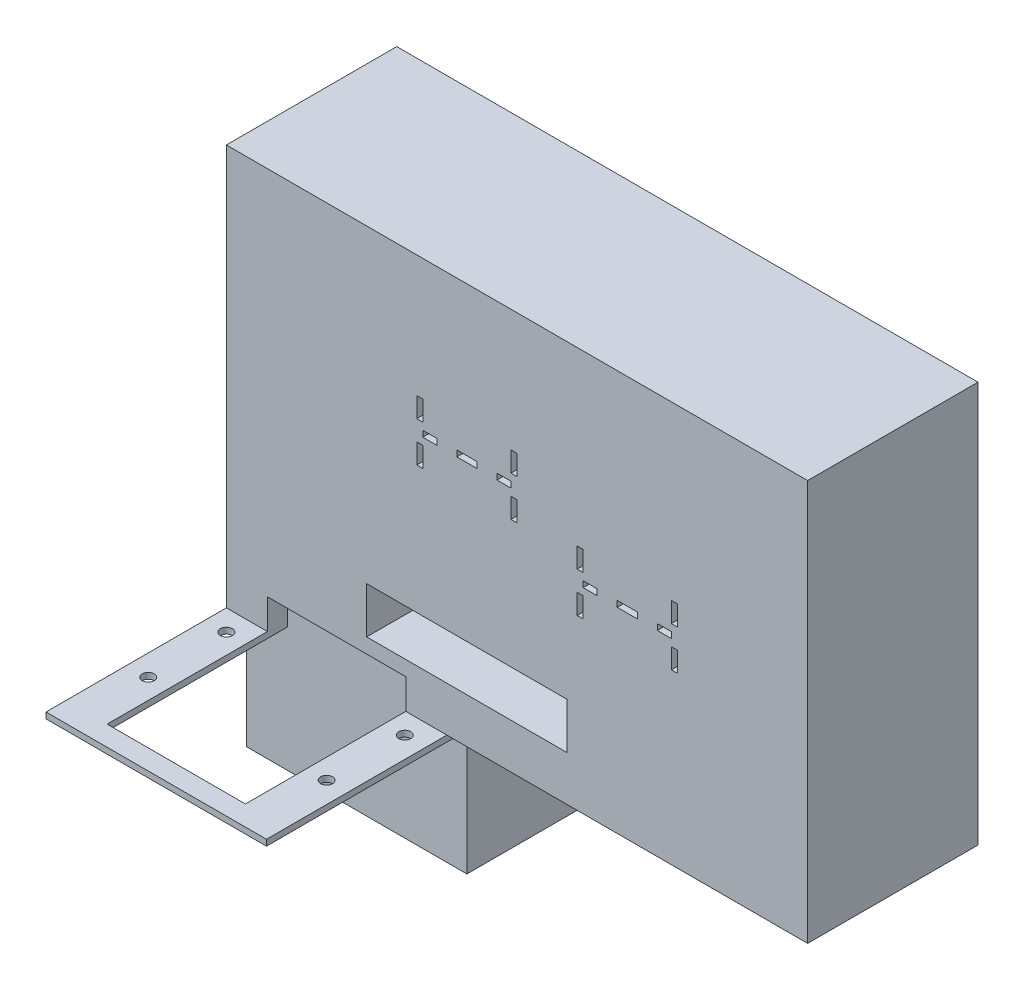
SolidWorks part; units mm, degrees
material "Cedro"
ref_plane "Alzado" through (0, 0, 0) normal (0, 0, 1) x (1, 0, 0)
ref_plane "Planta" through (0, 0, 0) normal (0, 1, 0) x (1, 0, 0)
ref_plane "Vista lateral" through (0, 0, 0) normal (1, 0, 0) x (0, 0, -1)
sketch "Croquis1" plane through (0, 0, 0) normal (0, 0, 1) x (1, 0, 0)
  line L1 (-85.6349, 58.6584) -> (24.3651, 58.6584)
  line L2 (-85.6349, 58.6584) -> (-85.6349, -6.3416)
  line L3 (-85.6349, -6.3416) -> (24.3651, -6.3416)
  line L4 (24.3651, 58.6584) -> (24.3651, -6.3416)
  line L5 (-85.6349, 58.6584) -> (24.3651, -6.3416) construction
  line L6 (-85.6349, -6.3416) -> (24.3651, 58.6584) construction
  point P0 (-30.6349, 26.1584)
  dimension "D1" = 65
  dimension "D2" = 110
extrude "Saliente-Extruir1" add sketch "Croquis1" along normal blind 75
sketch "Croquis3" plane through (0, 0, 75) normal (0, 0, 1) x (1, 0, 0)
  line L0 (-85.6349, 58.6584) -> (24.3651, 58.6584)
  line L1 (-85.6349, 58.6584) -> (-85.6349, 55.6584)
  line L2 (-85.6349, 58.6584) -> (-85.6349, -6.3416) construction
  line L3 (-85.6349, 55.6584) -> (24.3651, 55.6584)
  line L4 (24.3651, -6.3416) -> (24.3651, 58.6584) construction
  line L5 (24.3651, 55.6584) -> (24.3651, 58.6584)
  dimension "D1" = 3
extrude "Saliente-Extruir2" add sketch "Croquis3" along normal blind 70
sketch "Croquis4" plane through (0, 55.6584, 0) normal (0, -1, 0) x (1, 0, 0)
  line L3 (-65.1349, 134.5) -> (-65.1349, 75)
  line L6 (-85.6349, 75) -> (24.3651, 75) construction
  line L7 (-65.1349, 134.5) -> (-65.1349, 145)
  line L8 (-85.6349, 145) -> (24.3651, 145) construction
  line L9 (-65.1349, 75) -> (3.8651, 75)
  line L11 (-65.1349, 145) -> (3.8651, 145)
  line L13 (3.8651, 138) -> (3.8651, 145)
  line L14 (3.8651, 138) -> (3.8651, 75)
  circle A0 centre (-75.1349, 134.5) radius 3
  circle A1 centre (-75.1349, 95.5) radius 3
  circle A2 centre (13.8651, 134.5) radius 3
  circle A3 centre (13.8651, 95.5) radius 3
  dimension "D5" = 6
  dimension "D6" = 6
  dimension "D7" = 6
  dimension "D8" = 6
  dimension "D1" = 10
  dimension "D3" = 39
  dimension "D4" = 89
extrude "Cortar-Extruir1" cut sketch "Croquis4" against normal blind 70
sketch "Croquis6" plane through (0, 58.6584, 0) normal (0, 1, 0) x (1, 0, 0)
  line L0 (-85.6349, -145) -> (-85.6349, -175)
  line L1 (-85.6349, -175) -> (24.3651, -175)
  line L2 (24.3651, -175) -> (24.3651, -145)
  line L3 (24.3651, -145) -> (3.8651, -145)
  line L4 (-65.1349, -145) -> (-65.1349, -165)
  line L5 (-65.1349, -165) -> (3.8651, -165)
  line L6 (3.8651, -165) -> (3.8651, -145)
  line L7 (-65.1349, -145) -> (-85.6349, -145)
  dimension "D1" = 30
  dimension "D2" = 20
extrude "Saliente-Extruir3" add sketch "Croquis6" against normal blind 3
sketch "Croquis7" plane through (0, 58.6584, 0) normal (0, 1, 0) x (1, 0, 0)
  line L0 (-85.6349, 0) -> (204.3651, 0)
  line L1 (-85.6349, 0) -> (-85.6349, -85)
  line L2 (-85.6349, -175) -> (-85.6349, 0) construction
  line L3 (-85.6349, -85) -> (204.3651, -85)
  line L4 (204.3651, -85) -> (204.3651, 0)
  dimension "D1" = 290
  dimension "D2" = 85
extrude "Saliente-Extruir4" add sketch "Croquis7" along normal blind 200
sketch "Croquis8" plane through (0, 0, 85) normal (0, 0, 1) x (1, 0, 0)
  line L0 (-65.1349, 58.6584) -> (-65.1349, 73.6584)
  line L1 (-65.1349, 73.6584) -> (3.8651, 73.6584)
  line L2 (3.8651, 58.6584) -> (3.8651, 73.6584)
  line L3 (-65.1349, 58.6584) -> (3.8651, 58.6584)
  dimension "D1" = 15
  dimension "D2" = 15
extrude "Cortar-Extruir2" cut sketch "Croquis8" against normal blind 10
sketch "Croquis10" plane through (0, 0, 85) normal (0, 0, 1) x (1, 0, 0)
  line L1 (-0.6349, 81.0942) -> (-15.6349, 81.0942)
  line L2 (69.3651, 81.0942) -> (-0.6349, 81.0942)
  line L4 (-15.6349, 81.0942) -> (-15.6349, 104.0942)
  line L5 (-15.6349, 104.0942) -> (-0.6349, 104.0942)
  line L6 (69.3651, 81.0942) -> (84.3651, 81.0942)
  line L7 (69.3651, 104.0942) -> (-0.6349, 104.0942)
  line L8 (84.3651, 81.0942) -> (84.3651, 104.0942)
  line L11 (84.3651, 104.0942) -> (69.3651, 104.0942)
  dimension "D1" = 15
  dimension "D3" = 15
extrude "Cortar-Extruir3" cut sketch "Croquis10" against normal blind 50
sketch "Croquis12" plane through (0, 0, 85) normal (0, 0, 1) x (1, 0, 0)
  line L0 (34.3651, 104.0942) -> (34.3651, 258.6584) construction
  line L1 (84.3651, 104.0942) -> (-15.6349, 104.0942) construction
  line L2 (-85.6349, 258.6584) -> (204.3651, 258.6584) construction
  line L3 (29.3651, 181.3763) -> (39.3651, 181.3763)
  line L4 (39.3651, 181.3763) -> (39.3651, 184.3763)
  line L5 (39.3651, 184.3763) -> (29.3651, 184.3763)
  line L6 (39.3651, 181.3763) -> (49.3651, 181.3763) construction
  line L7 (49.3651, 181.3763) -> (49.3651, 184.3763)
  line L8 (49.3651, 184.3763) -> (56.3651, 184.3763)
  line L9 (56.3651, 184.3763) -> (56.3651, 181.3763)
  line L10 (56.3651, 181.3763) -> (49.3651, 181.3763)
  line L11 (56.3651, 181.3763) -> (56.3651, 177.8763) construction
  line L12 (56.3651, 177.8763) -> (59.3651, 177.8763)
  line L13 (56.3651, 177.8763) -> (56.3651, 167.8763)
  line L14 (56.3651, 167.8763) -> (59.3651, 167.8763)
  line L15 (59.3651, 167.8763) -> (59.3651, 177.8763)
  line L16 (56.3651, 182.8763) -> (59.3651, 182.8763) construction
  line L17 (56.3651, 184.3763) -> (56.3651, 187.8763) construction
  line L18 (59.3651, 197.8763) -> (59.3651, 187.8763)
  line L19 (56.3651, 197.8763) -> (59.3651, 197.8763)
  line L20 (56.3651, 187.8763) -> (56.3651, 197.8763)
  line L21 (56.3651, 187.8763) -> (59.3651, 187.8763)
  line L22 (12.3651, 184.3763) -> (12.3651, 187.8763) construction
  line L23 (12.3651, 182.8763) -> (9.3651, 182.8763) construction
  line L24 (12.3651, 181.3763) -> (12.3651, 177.8763) construction
  line L25 (12.3651, 187.8763) -> (9.3651, 187.8763)
  line L26 (12.3651, 187.8763) -> (12.3651, 197.8763)
  line L27 (12.3651, 197.8763) -> (9.3651, 197.8763)
  line L28 (9.3651, 197.8763) -> (9.3651, 187.8763)
  line L29 (9.3651, 167.8763) -> (9.3651, 177.8763)
  line L30 (12.3651, 167.8763) -> (9.3651, 167.8763)
  line L31 (12.3651, 177.8763) -> (12.3651, 167.8763)
  line L32 (12.3651, 177.8763) -> (9.3651, 177.8763)
  line L33 (12.3651, 181.3763) -> (19.3651, 181.3763)
  line L34 (12.3651, 184.3763) -> (12.3651, 181.3763)
  line L35 (19.3651, 184.3763) -> (12.3651, 184.3763)
  line L36 (19.3651, 181.3763) -> (19.3651, 184.3763)
  line L37 (29.3651, 181.3763) -> (19.3651, 181.3763) construction
  line L38 (29.3651, 181.3763) -> (29.3651, 184.3763)
  line L39 (119.3651, 159.3763) -> (109.3651, 159.3763)
  line L40 (74.3651, 184.3763) -> (114.3651, 184.3763) construction
  line L41 (114.3651, 184.3763) -> (114.3651, 159.3763) construction
  line L42 (129.3651, 159.3763) -> (136.3651, 159.3763)
  line L43 (92.3651, 172.8763) -> (89.3651, 172.8763)
  line L44 (92.3651, 157.8763) -> (89.3651, 157.8763) construction
  line L45 (89.3651, 142.8763) -> (89.3651, 152.8763)
  line L46 (92.3651, 156.3763) -> (99.3651, 156.3763)
  line L47 (92.3651, 142.8763) -> (89.3651, 142.8763)
  line L48 (119.3651, 156.3763) -> (129.3651, 156.3763) construction
  line L49 (136.3651, 172.8763) -> (139.3651, 172.8763)
  line L50 (136.3651, 156.3763) -> (136.3651, 152.8763) construction
  line L51 (129.3651, 156.3763) -> (129.3651, 159.3763)
  line L52 (136.3651, 152.8763) -> (139.3651, 152.8763)
  line L53 (99.3651, 159.3763) -> (92.3651, 159.3763)
  line L54 (139.3651, 142.8763) -> (139.3651, 152.8763)
  line L55 (109.3651, 156.3763) -> (119.3651, 156.3763)
  line L56 (92.3651, 162.8763) -> (89.3651, 162.8763)
  line L57 (92.3651, 159.3763) -> (92.3651, 156.3763)
  line L58 (136.3651, 162.8763) -> (136.3651, 172.8763)
  line L59 (92.3651, 152.8763) -> (92.3651, 142.8763)
  line L60 (136.3651, 152.8763) -> (136.3651, 142.8763)
  line L61 (92.3651, 152.8763) -> (89.3651, 152.8763)
  line L62 (99.3651, 156.3763) -> (99.3651, 159.3763)
  line L63 (92.3651, 156.3763) -> (92.3651, 152.8763) construction
  line L64 (139.3651, 172.8763) -> (139.3651, 162.8763)
  line L65 (89.3651, 172.8763) -> (89.3651, 162.8763)
  line L66 (119.3651, 156.3763) -> (119.3651, 159.3763)
  line L67 (92.3651, 162.8763) -> (92.3651, 172.8763)
  line L68 (92.3651, 159.3763) -> (92.3651, 162.8763) construction
  line L69 (136.3651, 142.8763) -> (139.3651, 142.8763)
  line L70 (136.3651, 157.8763) -> (139.3651, 157.8763) construction
  line L71 (136.3651, 162.8763) -> (139.3651, 162.8763)
  line L72 (136.3651, 159.3763) -> (136.3651, 162.8763) construction
  line L73 (136.3651, 159.3763) -> (136.3651, 156.3763)
  line L74 (109.3651, 156.3763) -> (109.3651, 159.3763)
  line L75 (109.3651, 156.3763) -> (99.3651, 156.3763) construction
  line L76 (136.3651, 156.3763) -> (129.3651, 156.3763)
  point P10 (34.3651, 181.3763)
  point P40 (34.3651, 184.3763)
  point P46 (114.3651, 156.3763)
  point P76 (114.3651, 159.3763)
  dimension "D1" = 154.5642
  dimension "D2" = 5
  dimension "D3" = 3
  dimension "D4" = 10
  dimension "D5" = 7
  dimension "D6" = 3.5
  dimension "D7" = 3
  dimension "D8" = 10
  dimension "D9" = 3
  dimension "D10" = 5
  dimension "D11" = 40
  dimension "D12" = 25
  dimension "D13" = 3
  dimension "D14" = 10
  dimension "D15" = 7
  dimension "D16" = 3.5
  dimension "D17" = 3
  dimension "D18" = 10
  dimension "D19" = 3
extrude "Cortar-Extruir4" cut sketch "Croquis12" against normal blind 3
